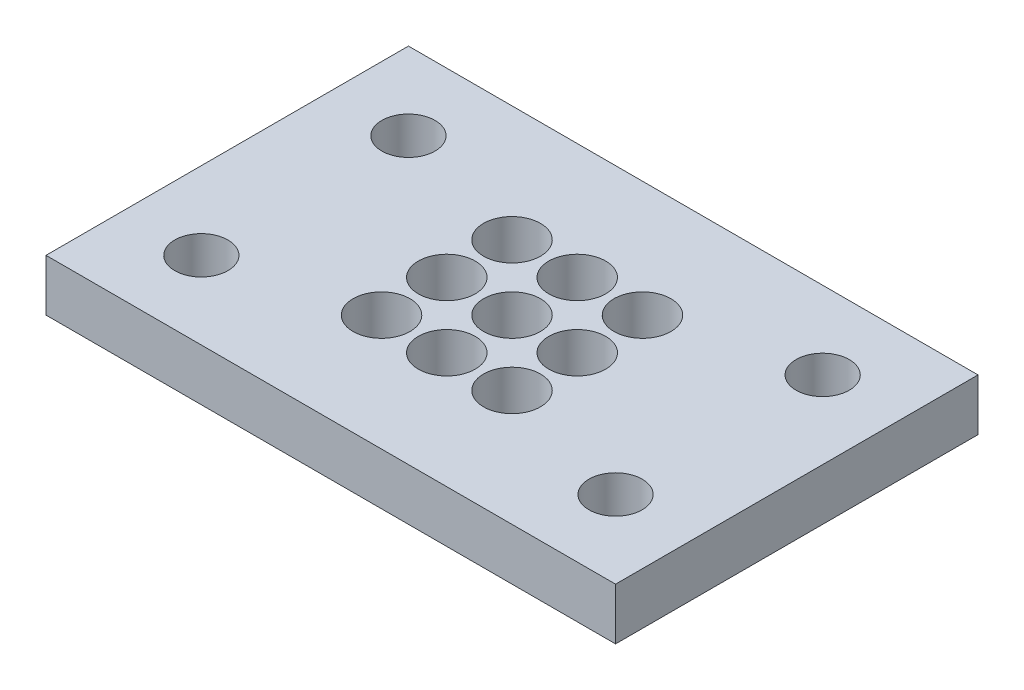
SolidWorks part; units mm, degrees
ref_plane "Front Plane" through (0, 0, 0) normal (0, 0, 1) x (1, 0, 0)
ref_plane "Top Plane" through (0, 0, 0) normal (0, 1, 0) x (1, 0, 0)
ref_plane "Right Plane" through (0, 0, 0) normal (1, 0, 0) x (0, 0, -1)
sketch "Sketch1" plane through (0, 0, 0) normal (0, 1, 0) x (1, 0, 0)
  line L0 (9.525, 34.925) -> (0, 34.925) construction
  line L1 (0, 0) -> (69.85, 0)
  line L2 (0, 0) -> (0, 44.45)
  line L3 (0, 44.45) -> (69.85, 44.45)
  line L4 (69.85, 0) -> (69.85, 44.45)
  line L5 (9.525, 34.925) -> (60.325, 34.925) construction
  line L6 (9.525, 34.925) -> (9.525, 9.525) construction
  line L7 (9.525, 9.525) -> (60.325, 9.525) construction
  line L8 (60.325, 34.925) -> (60.325, 9.525) construction
  line L9 (9.525, 34.925) -> (9.525, 44.45) construction
  circle A0 centre (9.525, 34.925) radius 3.2639
  circle A1 centre (60.325, 34.925) radius 3.2639
  circle A2 centre (9.525, 9.525) radius 3.2639
  circle A3 centre (60.325, 9.525) radius 3.2639
  circle A4 centre (34.925, 22.225) radius 3.4925
  circle A5 centre (42.925, 22.225) radius 3.4925
  circle A6 centre (42.925, 30.225) radius 3.4925
  circle A7 centre (34.925, 30.225) radius 3.4925
  circle A8 centre (26.925, 22.225) radius 3.4925
  circle A9 centre (26.925, 30.225) radius 3.4925
  circle A10 centre (34.925, 30.225) radius 3.4925
  circle A11 centre (42.925, 22.225) radius 3.4925
  circle A12 centre (42.925, 14.225) radius 3.4925
  circle A13 centre (34.925, 14.225) radius 3.4925
  circle A14 centre (26.925, 22.225) radius 3.4925
  circle A15 centre (26.925, 14.225) radius 3.4925
  circle A16 centre (34.925, 14.225) radius 3.4925
  point P13 (34.925, 34.925)
  point P14 (34.925, 44.45)
  point P20 (69.85, 22.225)
  dimension "D5" = 6.5278
  dimension "D6" = 6.985
  dimension "D1" = 69.85
  dimension "D2" = 44.45
  dimension "D3" = 50.8
  dimension "D4" = 25.4
  dimension "D7" = 2
  dimension "D8" = 2
  dimension "D9" = 2
  dimension "D10" = 2
  dimension "D11" = 2
  dimension "D12" = 2
  dimension "D13" = 2
  dimension "D14" = 2
extrude "Boss-Extrude1" add sketch "Sketch1" along normal blind 6.35 contours L1 L4 L3 L2 A15 A13 A12 A9 A8 A7 A6 A5 A4 A3 A2 A1 A0 region at (0.8279, 0, -22.225)
